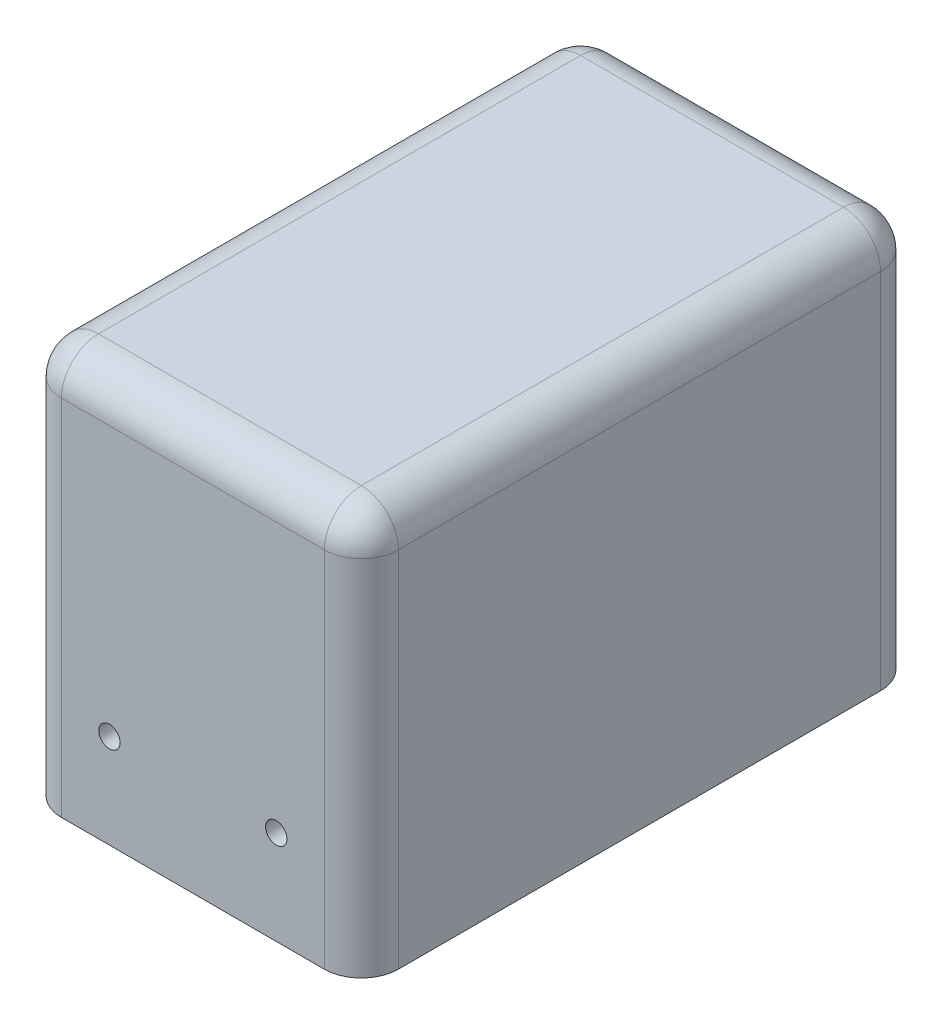
SolidWorks part; units mm, degrees
ref_plane "Front Plane" through (0, 0, 0) normal (0, 0, 1) x (1, 0, 0)
ref_plane "Top Plane" through (0, 0, 0) normal (0, 1, 0) x (1, 0, 0)
ref_plane "Right Plane" through (0, 0, 0) normal (1, 0, 0) x (0, 0, -1)
sketch "Sketch1" plane through (0, 0, 0) normal (0, 1, 0) x (1, 0, 0)
  line L1 (-18.175, 30) -> (18.175, 30)
  line L2 (-18.175, 30) -> (-18.175, -30)
  line L3 (-18.175, -30) -> (18.175, -30)
  line L4 (18.175, 30) -> (18.175, -30)
  line L5 (-18.175, 30) -> (18.175, -30) construction
  line L6 (-18.175, -30) -> (18.175, 30) construction
  line L7 (-15, 26.825) -> (15, 26.825)
  line L8 (-15, 26.825) -> (-15, -26.825)
  line L9 (-15, -26.825) -> (15, -26.825)
  line L10 (15, 26.825) -> (15, -26.825)
  line L11 (-15, 26.825) -> (15, -26.825) construction
  line L12 (-15, -26.825) -> (15, 26.825) construction
  point P0 (0, 0)
  point P6 (0, 0)
  dimension "D1" = 3.175
  dimension "D2" = 3.175
  dimension "D3" = 30
  dimension "D4" = 60
extrude "Boss-Extrude1" add sketch "Sketch1" along normal blind 40
sketch "Sketch2" plane through (0, 40, 0) normal (0, 1, 0) x (1, 0, 0)
  line L1 (-18.175, -30) -> (18.175, -30)
  line L2 (-18.175, -30) -> (-18.175, 30)
  line L3 (-18.175, 30) -> (18.175, 30)
  line L4 (18.175, -30) -> (18.175, 30)
extrude "Boss-Extrude2" add sketch "Sketch2" along normal blind 3.175
fillet "Fillet1" radius 4 8 edges at (-18.175, 43.175, 0) (-18.175, 21.5875, -30) (0, 43.175, -30) (18.175, 21.5875, -30) (18.175, 43.175, 0) (0, 43.175, 30) (18.175, 21.5875, 30) (-18.175, 21.5875, 30)
sketch "Sketch3" plane through (0, 0, 30) normal (0, 0, 1) x (1, 0, 0)
  line L0 (0, 0) -> (0, 39.175) construction
  line L1 (-14.175, 0) -> (14.175, 0) construction
  line L2 (14.175, 39.175) -> (-14.175, 39.175) construction
  circle A0 centre (-9, 10.145) radius 1.15
  circle A1 centre (9, 10.145) radius 1.15
  dimension "D1" = 2.3
  dimension "D2" = 9
  dimension "D3" = 10.145
extrude "Cut-Extrude1" cut sketch "Sketch3" against normal up to surface (3.175 mm away) up to face at (0, 20, 26.825)
sketch "Sketch4" plane through (0, 0, 0) normal (0, -1, 0) x (1, 0, 0)
  line L0 (0, 30) -> (0, -30) construction
  line L1 (-14.175, 30) -> (14.175, 30) construction
  line L2 (14.175, -30) -> (-14.175, -30) construction
  line L3 (-18.175, 0) -> (18.175, 0) construction
  line L4 (-18.175, -26) -> (-18.175, 26) construction
  line L5 (18.175, 26) -> (18.175, -26) construction
  line L6 (-13.175, -17.225) -> (-15, -17.225)
  line L7 (-15, -26.825) -> (-15, 26.825) construction
  line L8 (-13.175, -24.425) -> (-15, -24.425)
  line L9 (-15, -17.225) -> (-15, -24.425)
  line L10 (13.175, -24.425) -> (15, -24.425)
  line L11 (15, -17.225) -> (15, -24.425)
  line L12 (13.175, -17.225) -> (15, -17.225)
  line L13 (15, -26.825) -> (-15, -26.825) construction
  arc A0 (-13.175, -24.425) -> (-13.175, -17.225) centre (-13.175, -20.825) ccw
  arc A1 (13.175, -24.425) -> (13.175, -17.225) centre (13.175, -20.825) cw
  point P24 (0, 0)
  dimension "D1" = 7.2
  dimension "D2" = 5
  dimension "D3" = 6
extrude "Boss-Extrude3" add sketch "Sketch4" against normal blind 3.5
sketch "Sketch5" plane through (0, 0, 0) normal (0, -1, 0) x (1, 0, 0)
  line L0 (0, 30) -> (0, -30) construction
  line L1 (-14.175, 30) -> (14.175, 30) construction
  line L2 (14.175, -30) -> (-14.175, -30) construction
  circle A0 centre (-13.175, -20.825) radius 3.05
  circle A1 centre (13.175, -20.825) radius 3.05
  dimension "D1" = 6.1
extrude "Cut-Extrude2" cut sketch "Sketch5" against normal blind 2.7
